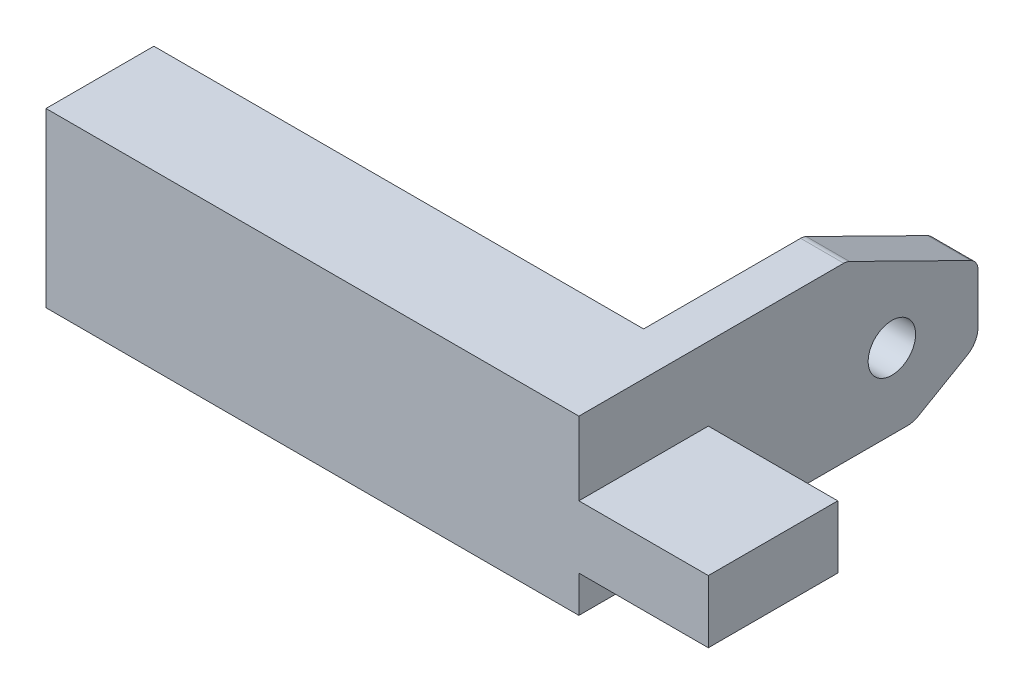
SolidWorks part; units mm, degrees
ref_plane "Front Plane" through (0, 0, 0) normal (0, 0, 1) x (1, 0, 0)
ref_plane "Top Plane" through (0, 0, 0) normal (0, 1, 0) x (1, 0, 0)
ref_plane "Right Plane" through (0, 0, 0) normal (1, 0, 0) x (0, 0, -1)
sketch "Sketch1" plane through (0, 0, 0) normal (1, 0, 0) x (0, 0, -1)
  line L1 (-35.9146, 20.1296) -> (56.5854, 20.1296)
  line L2 (-35.9146, 20.1296) -> (-35.9146, -19.8704)
  line L3 (-35.9146, -19.8704) -> (56.5854, -19.8704)
  line L4 (56.5854, 20.1296) -> (56.5854, -19.8704)
  dimension "D1" = 92.5
  dimension "D2" = 40
extrude "Boss-Extrude1" add sketch "Sketch1" along normal blind 10
sketch "Sketch4" plane through (0, 0, 0) normal (-1, 0, 0) x (0, 0, 1)
  line L11 (-56.5854, 20.1296) -> (35.9146, 20.1296) construction
  line L12 (10.9146, 20.1296) -> (35.9146, 20.1296)
  line L13 (10.9146, 20.1296) -> (10.9146, -19.8704)
  line L14 (10.9146, -19.8704) -> (35.9146, -19.8704)
  line L15 (35.9146, 20.1296) -> (35.9146, -19.8704)
  line L16 (10.9146, 20.1296) -> (35.9146, -19.8704) construction
  line L17 (10.9146, -19.8704) -> (35.9146, 20.1296) construction
  line L18 (18.2146, 12.8296) -> (18.2146, -12.5704)
  line L19 (18.2146, -12.5704) -> (28.6146, -12.5704)
  line L20 (28.6146, 12.8296) -> (28.6146, -12.5704)
  line L21 (18.2146, 12.8296) -> (28.6146, 12.8296)
  point P4 (23.4146, 0.1296)
  dimension "D1" = 25
  dimension "D2" = 7.3
sketch "Sketch5" plane through (0, 0, 0) normal (-1, 0, 0) x (0, 0, 1)
  line L0 (35.9146, -19.8704) -> (-56.5854, -19.8704) construction
  line L2 (35.9146, 20.1296) -> (35.9146, -19.8704) construction
  circle A0 centre (-36.6254, -2.4304) radius 5.5
  dimension "D1" = 11
  dimension "D2" = 17.44
  dimension "D3" = 72.54
extrude "Cut-Extrude1" cut sketch "Sketch5" against normal blind 27
sketch "Sketch6" plane through (10, 0, 0) normal (1, 0, 0) x (0, 0, -1)
  line L0 (-35.9146, 20.1296) -> (-35.9146, -19.8704) construction
  line L1 (-5.9146, -2.8704) -> (-35.9146, -2.8704)
  line L2 (-5.9146, -2.8704) -> (-5.9146, 3.1296)
  line L3 (-5.9146, 3.1296) -> (-35.9146, 3.1296)
  line L4 (-35.9146, -2.8704) -> (-35.9146, 3.1296)
  line L5 (-5.9146, -2.8704) -> (-35.9146, 3.1296) construction
  line L6 (-5.9146, 3.1296) -> (-35.9146, -2.8704) construction
  line L8 (-35.9146, -19.8704) -> (56.5854, -19.8704) construction
  point P0 (-20.9146, 0.1296)
  dimension "D1" = 30
  dimension "D2" = 6
  dimension "D3" = 20
extrude "Boss-Extrude5" add sketch "Sketch6" along normal blind 30
sketch "Sketch7" plane through (0, -2.8704, 0) normal (0, -1, 0) x (1, 0, 0)
  line L1 (40, 35.9146) -> (10, 35.9146)
  line L2 (40, 35.9146) -> (40, 5.9146)
  line L3 (40, 5.9146) -> (10, 5.9146)
  line L4 (10, 35.9146) -> (10, 5.9146)
extrude "Boss-Extrude6" add sketch "Sketch7" along normal blind 8.5
extrude "Boss-Extrude7" add sketch "Sketch4" along normal blind 113.5
fillet "Fillet1" radius 3 4 edges at (-113.5, -12.5704, 23.4146) (-113.5, 0.1296, 28.6146) (-113.5, 12.8296, 23.4146) (-113.5, 0.1296, 18.2146)
chamfer "Chamfer1" distance 15 angle 63.75 1 edges at (5, 20.1296, -56.5854) first distance on face at (5, 0.1296, -56.5854)
fillet "Fillet3" radius 3 2 edges at (5, 20.1296, -26.1684) (5, 5.1296, -56.5854)
chamfer "Chamfer3" distance 15 angle 30 1 edges at (5, -19.8704, -56.5854) first distance on face at (-34.5, -19.8704, -3.252)
fillet "Fillet7" radius 5 2 edges at (5, -19.8704, -41.5854) (5, -11.2102, -56.5854)
